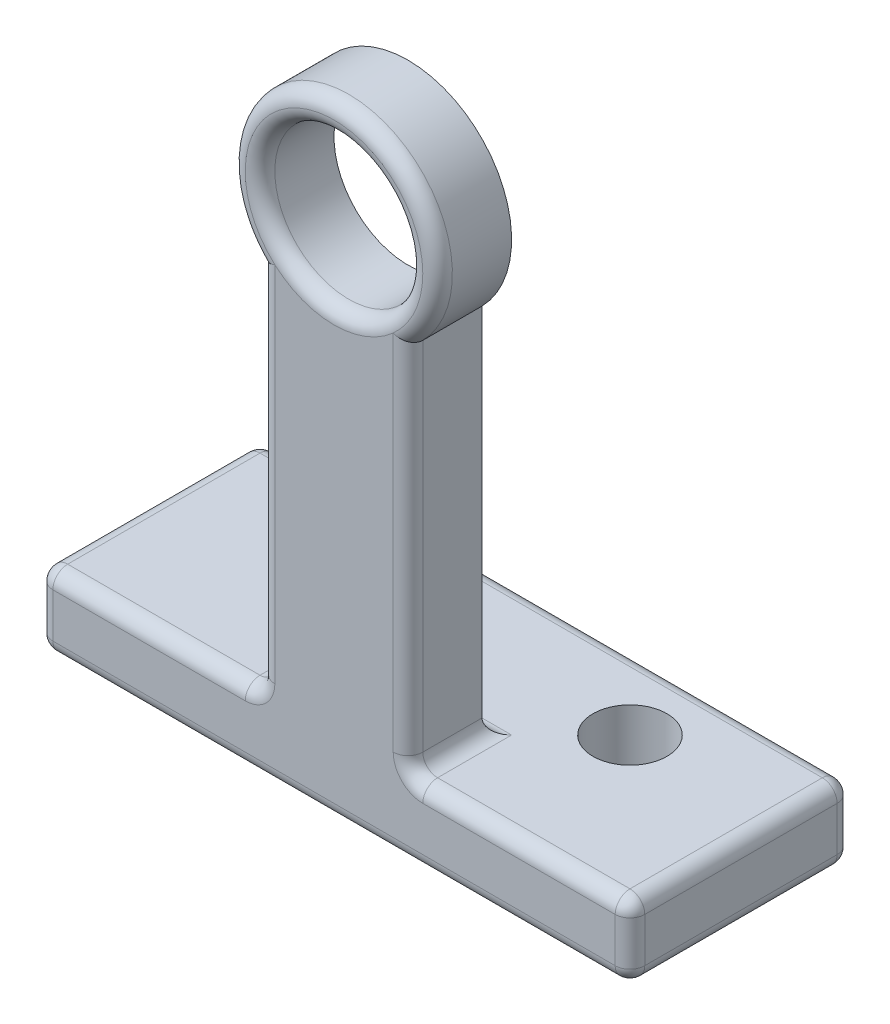
SolidWorks part; units mm, degrees
ref_plane "前视基准面" through (0, 0, 0) normal (0, 0, 1) x (1, 0, 0)
ref_plane "上视基准面" through (0, 0, 0) normal (0, 1, 0) x (1, 0, 0)
ref_plane "右视基准面" through (0, 0, 0) normal (1, 0, 0) x (0, 0, -1)
sketch "草图1" plane through (0, 0, 0) normal (0, 0, 1) x (1, 0, 0)
  line L0 (0, 0) -> (0, 35)
  line L1 (0, 0) -> (20, 0)
  line L2 (0, 0) -> (-20, 0)
  line L3 (-20, 0) -> (-20, 5)
  line L4 (-20, 5) -> (20, 5)
  line L5 (20, 5) -> (20, 0)
  line L6 (0, 5) -> (-5, 5)
  line L7 (-5, 5) -> (-5, 30.101)
  line L8 (0, 5) -> (5, 5)
  line L9 (5, 5) -> (5, 30.101)
  circle A0 centre (0, 35) radius 5
  circle A1 centre (0, 35) radius 7
extrude "凸台-拉伸1" add sketch "草图1" along normal blind 5 contours A1 L7 L4 L0 | A1 A0 | A1 L0 L4 L9 | L4 L3 L2 L0 | L5 L4 L0 L1 region at (-10, 2.5, 0) region at (10, 2.5, 0) region at (-2.5356, 16.8339, 0) region at (2.5356, 16.8339, 0) region at (-2.635, 28.7291, 0)
extrude "凸台-拉伸2" add sketch "草图1<3>" against normal blind 10 contours L5 L4 L0 L1 | L4 L3 L2 L0 region at (-10, 2.5, 0) region at (10, 2.5, 0)
sketch "草图1<3>" plane through (0, 0, 0) normal (0, 0, 1) x (1, 0, 0) same geometry as "草图1"
fillet "圆角1" radius 1 20 edges at (-20, 0, -2.5) (20, 0, -2.5) (5, 5, 2.5) (0, 5, 0) (-5, 5, 2.5) (-20, 5, -2.5) (20, 5, -2.5) (5, 35, 5) (12.5, 5, 5) (20, 2.5, 5) (0, 0, 5) (-20, 2.5, 5) (-12.5, 5, 5) (-5, 17.5505, 5) (0, 42, 5) (5, 17.5505, 5) (0, 5, -10) (-20, 2.5, -10) (0, 0, -10) (20, 2.5, -10)
sketch "草图2" plane through (0, 5, 0) normal (0, 1, 0) x (1, 0, 0)
  line L0 (0, 10) -> (0, 5)
  line L1 (-19, 10) -> (19, 10) construction
  line L2 (0, 5) -> (-10, 5)
  line L3 (0, 5) -> (10, 5)
  circle A0 centre (-10, 5) radius 2.5
  circle A1 centre (10, 5) radius 2.5
extrude "切除-拉伸1" cut sketch "草图2" against normal blind 10 contours A1 | A0 region at (-12.4293, 5, -5) region at (10, 5, -7.4293)
